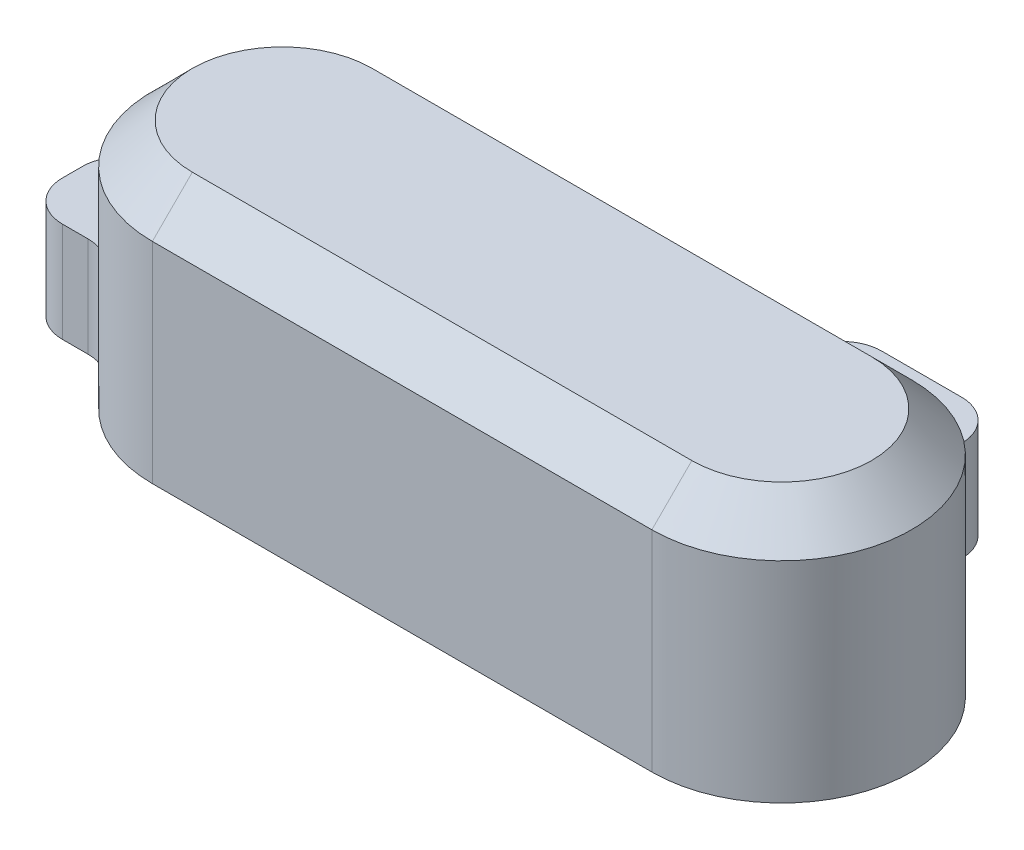
SolidWorks part; units mm, degrees
ref_plane "Plane XZ" through (0, 0, 0) normal (0, 0, 1) x (1, 0, 0)
ref_plane "Plane XY" through (0, 0, 0) normal (0, 1, 0) x (1, 0, 0)
ref_plane "Plane YZ" through (0, 0, 0) normal (1, 0, 0) x (0, 0, -1)
sketch "Sketch1" plane through (0, 0, 0) normal (0, 1, 0) x (1, 0, 0)
  line L0 (-3.175, 0) -> (3.175, 0) construction
  line L1 (-3.175, 1.905) -> (3.175, 1.905) construction
  line L2 (-3.175, -1.905) -> (3.175, -1.905) construction
  line L3 (-3.175, 1.651) -> (3.175, 1.651)
  line L4 (-3.175, -1.651) -> (3.175, -1.651)
  arc A0 (-3.175, 1.905) -> (-3.175, -1.905) centre (-3.175, 0) ccw construction
  arc A1 (3.175, -1.905) -> (3.175, 1.905) centre (3.175, 0) ccw construction
  arc A2 (3.175, -1.651) -> (3.175, 1.651) centre (3.175, 0) ccw
  arc A3 (-3.175, 1.651) -> (-3.175, -1.651) centre (-3.175, 0) ccw
  point P2 (0, 0)
  dimension "D1" = 1.905
  dimension "D2" = 6.35
  dimension "D3" = 0.254
extrude "Boss-Extrude1" add sketch "Sketch1" along normal blind 3.175
sketch "Sketch2" plane through (0, 0, 0) normal (0, -1, 0) x (1, 0, 0)
  line L0 (-3.175, 1.651) -> (3.175, 1.651) construction
  line L1 (0.762, 1.651) -> (2.794, 1.651) construction
  line L2 (0.762, 1.651) -> (0.762, 3.175) construction
  line L3 (0.762, 3.175) -> (2.794, 3.175) construction
  line L4 (2.794, 1.651) -> (2.794, 3.175) construction
  line L5 (-3.81, 0) -> (0, 0) construction
  line L6 (-3.81, 0.635) -> (-5.842, 0.635)
  line L7 (-3.81, 0.635) -> (-3.81, -0.635)
  line L8 (-3.81, -0.635) -> (-5.842, -0.635)
  line L9 (-5.842, 0.635) -> (-5.842, -0.635)
  line L10 (1.778, 3.175) -> (1.778, 1.651) construction
  line L11 (0.762, -3.175) -> (2.794, -3.175)
  line L12 (2.794, -1.651) -> (2.794, -3.175)
  line L13 (0.762, -1.651) -> (2.794, -1.651)
  line L14 (0.762, -1.651) -> (0.762, -3.175)
  dimension "D1" = 5.842
  dimension "D2" = 1.27
  dimension "D3" = 2.032
  dimension "D4" = 3.175
  dimension "D5" = 0.762
  dimension "D6" = 2.032
extrude "Boss-Extrude2" add sketch "Sketch2" against normal blind 1.27
chamfer "Chamfer1" distance 0.508 angle 45 4 edges at (0, 3.175, 1.651) (4.826, 3.175, 0) (-4.826, 3.175, 0) (0, 3.175, -1.651)
sketch "Sketch3" plane through (0, 3.175, 0) normal (0, 1, 0) x (1, 0, 0)
  line L0 (0, -1.016) -> (0, 1.016) construction
  line L1 (-3.1962, 1.016) -> (3.1962, 1.016) construction
  line L2 (-3.1962, 1.016) -> (-3.1962, -1.016) construction
  line L3 (-3.1962, -1.016) -> (3.1962, -1.016) construction
  line L4 (3.1962, 1.016) -> (3.1962, -1.016) construction
  text T0 "2" font "Calibri" height 2.032
  dimension "D1" = 2.032
fillet "Fillet1" radius 0.508 8 edges at (-5.842, 0.635, 0.635) (-4.699, 0.635, 0.635) (-4.699, 0.635, -0.635) (-5.842, 0.635, -0.635) (2.794, 0.635, -1.651) (2.794, 0.635, -3.175) (0.762, 0.635, -3.175) (0.762, 0.635, -1.651)
